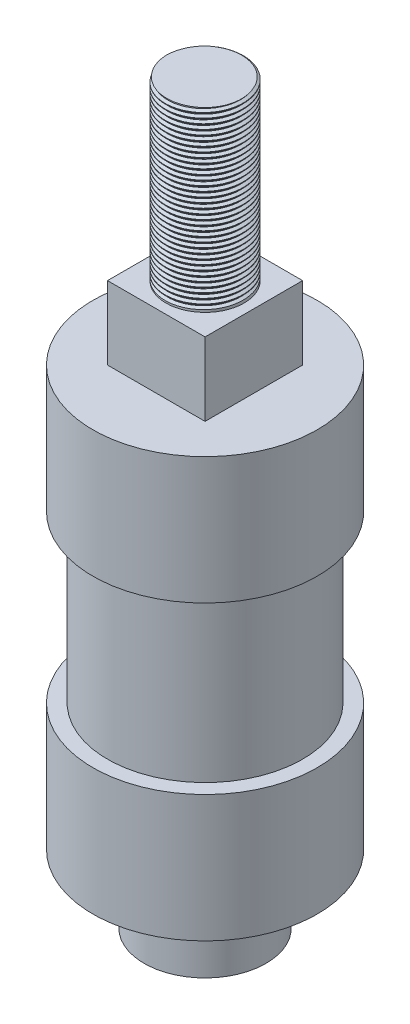
SolidWorks part; units mm, degrees
ref_plane "Front Plane" through (0, 0, 0) normal (0, 0, 1) x (1, 0, 0)
ref_plane "Top Plane" through (0, 0, 0) normal (0, 1, 0) x (1, 0, 0)
ref_plane "Right Plane" through (0, 0, 0) normal (1, 0, 0) x (0, 0, -1)
sketch "Sketch1" plane through (0, 0, 0) normal (0, 0, 1) x (1, 0, 0)
  line L0 (0, 0) -> (13734.5219, 0) construction
  line L1 (0, 0) -> (0, 13734.5219) construction
  line L2 (0, 0) -> (12.5, 0)
  line L3 (12.5, 0) -> (12.5, 14)
  line L4 (12.5, 14) -> (23, 14)
  line L5 (23, 14) -> (23, 40)
  line L6 (23, 40) -> (20, 40)
  line L7 (20, 40) -> (20, 74)
  line L8 (20, 74) -> (23, 74)
  line L9 (23, 74) -> (23, 100)
  line L10 (23, 100) -> (8, 100)
  line L11 (8, 100) -> (8, 151)
  line L12 (8, 151) -> (0, 151)
  line L13 (0, 0) -> (0, 151)
  dimension "D1" = 25
  dimension "D2" = 14
  dimension "D3" = 26
  dimension "D4" = 46
  dimension "D5" = 100
  dimension "D6" = 40
  dimension "D7" = 26
  dimension "D8" = 51
  dimension "D9" = 16
revolve "Revolve2" add sketch "Sketch1" angle 360 about L13
sketch "Sketch8" plane through (0, 0, 0) normal (0, -1, 0) x (1, 0, 0)
  point P0 (0, 0)
hole_wizard "M16 Tapped Hole2" positions "Sketch8" profile "Sketch7" tap size "M16" standard "ISO"
sketch "Sketch7" plane through (0, 0, 0) normal (1, 0, 0) x (0, 0, -1)
  line L0 (0, 0) -> (0, 24.206)
  line L1 (0, 24.206) -> (7, 20)
  line L2 (7, 20) -> (7, 0)
  line L5 (7, 0) -> (0, 0)
  line L10 (0, 24.206) -> (-7, 20) construction
  line L11 (0, -6.35) -> (0, 107.95) construction
  dimension "Tap Drill Dia." = 14
  dimension "Tap Drill Depth" = 20
  dimension "Drill Angle" = 118
cosmetic thread "Hole Thread2" parameters "D1"=32, "D2"=16
sketch "Sketch10" plane through (0, 100, 0) normal (0, 1, 0) x (1, 0, 0)
  line L1 (10, -10) -> (-10, -10)
  line L2 (10, -10) -> (10, 10)
  line L3 (10, 10) -> (-10, 10)
  line L4 (-10, -10) -> (-10, 10)
  line L5 (10, -10) -> (-10, 10) construction
  line L6 (10, 10) -> (-10, -10) construction
  point P0 (0, 0)
  dimension "D1" = 20
extrude "Boss-Extrude2" add sketch "Sketch10" along normal blind 15
thread "Thread1" pitch 1 method cut profile "Thread Profile1" start angle 0, offset 2, length 37, pitch 1, diameter 16
ref_plane "Plane1" through (-8, 153, 0) normal (0, 0, 1) x (-1, 0, 0)
sketch "Thread Profile1" plane through (-8, 153, 0) normal (0, 0, 1) x (-1, 0, 0)
  line L0 (0, 0) -> (0, 1) construction
  line L11 (0, 0) -> (0, 0.875)
  line L12 (0, 0.875) -> (-0.5413, 0.5625)
  line L13 (-0.5413, 0.5625) -> (-0.5413, 0.3125)
  line L15 (-0.5413, 0.3125) -> (0, 0)
  line L17 (-0.5413, 0.4375) -> (0, 0.4375) construction
  point P2 (0, 0)
  dimension "Pitch" = 1
  dimension "Profile_Angle" = 60
  dimension "Profile_Land" = 0.25
  dimension "Profile_Height" = 0.5413
